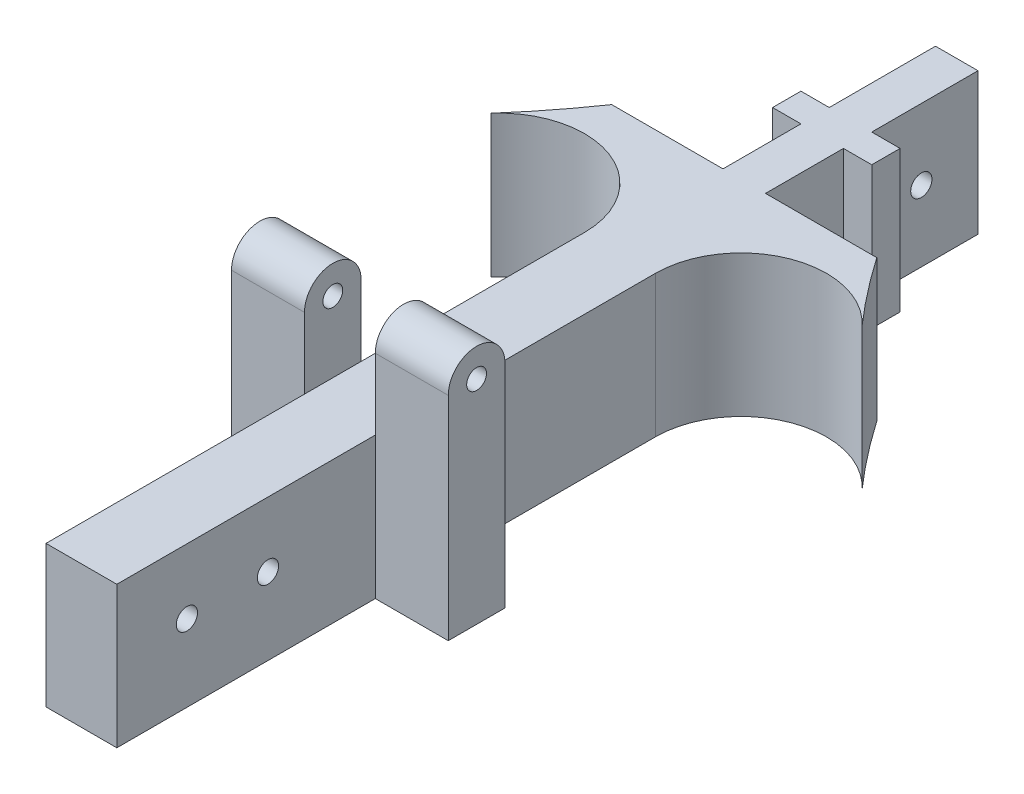
SolidWorks part; units mm, degrees
ref_plane "Plan de face" through (0, 0, 0) normal (0, 0, 1) x (1, 0, 0)
ref_plane "Plan de dessus" through (0, 0, 0) normal (0, 1, 0) x (1, 0, 0)
ref_plane "Plan de droite" through (0, 0, 0) normal (1, 0, 0) x (0, 0, -1)
sketch "Esquisse1" plane through (0, 0, 0) normal (0, 1, 0) x (1, 0, 0)
  line L0 (-3, 84.3983) -> (-3, 69.3983)
  line L1 (-3, 84.3983) -> (0, 84.3983)
  line L2 (-3, 65.3983) -> (-3, 54.3983)
  line L3 (-5, -39.1827) -> (0, -39.1827)
  line L4 (0, 84.3983) -> (0, -39.1827)
  line L5 (-3, 69.3983) -> (-7, 69.3983)
  line L6 (-3, 54.3983) -> (-18.71, 54.3983)
  line L7 (-3, 65.3983) -> (-7, 65.3983)
  line L8 (-7, 69.3983) -> (-7, 65.3983)
  line L9 (-5, 36.8425) -> (-5, -39.1827)
  arc A0 (-26.1833, 44.8157) -> (-18.71, 54.3983) centre (-105.5, 114.3795) ccw
  arc A1 (-5, 36.8425) -> (-26.1833, 44.8157) centre (-17.0922, 36.8425) ccw
  dimension "D7" = 211
  dimension "D1" = 3
  dimension "D2" = 4
  dimension "D3" = 4
  dimension "D4" = 15
  dimension "D5" = 11
  dimension "D6" = 15.71
extrude "Boss.-Extru.1" add sketch "Esquisse1" along normal blind 20
mirror "Symétrie1" about plane through (0, 20, -84.3983) normal (-1, 0, 0) of "Boss.-Extru.1"
sketch "Esquisse3" plane through (-3, 0, 0) normal (-1, 0, 0) x (0, 0, 1)
  line L2 (-84.3983, 20) -> (-69.3983, 20) construction
  line L3 (-65.3983, 20) -> (-54.3983, 20) construction
  line L4 (-84.3983, 20) -> (-84.3983, 0) construction
  circle A0 centre (-76.3983, 10) radius 1.5
  circle A1 centre (-60.3983, 10) radius 1.5
  dimension "D1" = 3
  dimension "D2" = 3
  dimension "D3" = 10
  dimension "D4" = 10
  dimension "D5" = 8
  dimension "D6" = 24
extrude "Enlèv. mat.-Extru.3" cut sketch "Esquisse3" against normal blind 20
sketch "Esquisse4" plane through (-5, 0, 0) normal (-1, 0, 0) x (0, 0, 1)
  circle A0 centre (29.292, 10.84) radius 1.5
extrude "Enlèv. mat.-Extru.4" cut sketch "Esquisse4" against normal blind 10
sketch "Esquisse5" plane through (-5, 0, 0) normal (-1, 0, 0) x (0, 0, 1)
  circle A0 centre (17.842, 10.84) radius 1.5
extrude "Enlèv. mat.-Extru.5" cut sketch "Esquisse5" against normal blind 10
sketch "Esquisse6" plane through (5, 0, 0) normal (1, 0, 0) x (0, 0, -1)
  line L0 (36.8425, 0) -> (-39.1827, 0) construction
  line L1 (5.3082, 0) -> (-2.6918, 0)
  line L2 (5.3082, 0) -> (5.3082, 30)
  line L4 (-2.6918, 0) -> (-2.6918, 30)
  arc A0 (-2.6918, 30) -> (5.3082, 30) centre (1.3082, 30) cw
  circle A1 centre (1.3082, 30) radius 1.4
  dimension "D2" = 30
  dimension "D1" = 8
ref_plane "Plan1" through (0, 0, 0) normal (-1, 0, 0) x (0, 0, 1)
extrude "Boss.-Extru.2" add sketch "Esquisse6" along normal blind 10.3
mirror "Symétrie2" about plane through (0, 0, 0) normal (-1, 0, 0) of "Boss.-Extru.2"
